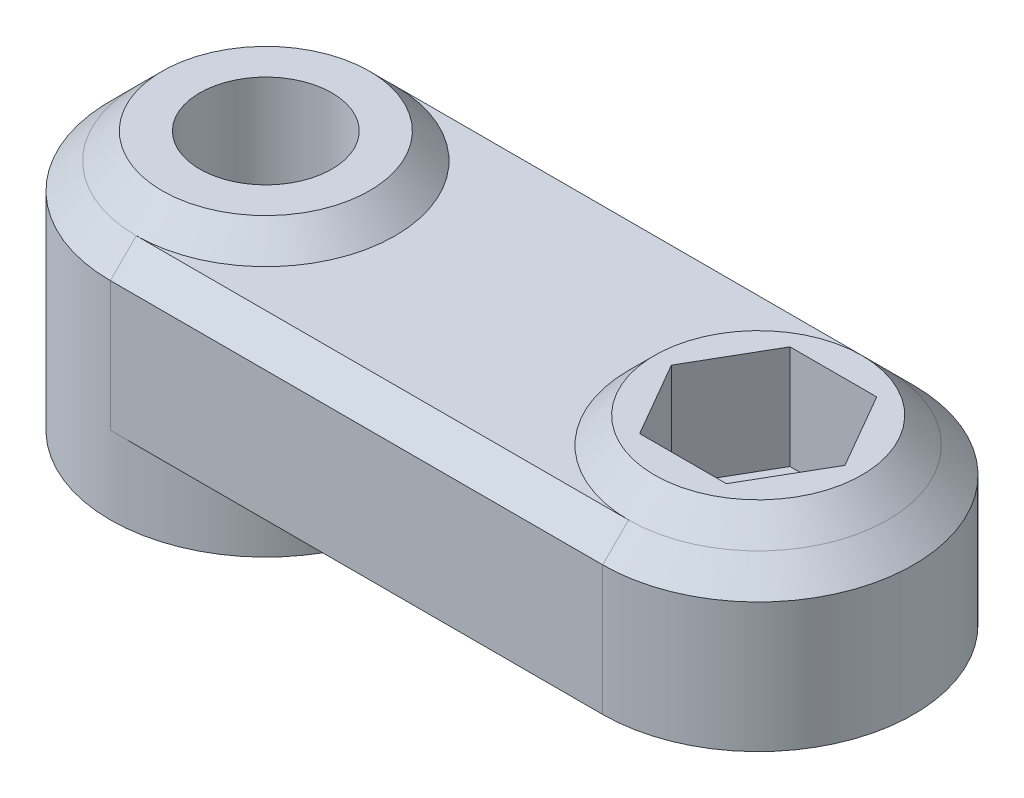
SolidWorks part; units mm, degrees
ref_plane "前视基准面" through (0, 0, 0) normal (0, 0, 1) x (1, 0, 0)
ref_plane "上视基准面" through (0, 0, 0) normal (0, 1, 0) x (1, 0, 0)
ref_plane "右视基准面" through (0, 0, 0) normal (1, 0, 0) x (0, 0, -1)
sketch "草图1" plane through (0, 0, 0) normal (0, 1, 0) x (1, 0, 0)
  line L0 (0, 0) -> (19, 0) construction
  line L1 (0, 6) -> (19, 6)
  line L2 (0, -6) -> (19, -6)
  arc A0 (0, 6) -> (0, -6) centre (0, 0) ccw
  arc A1 (19, -6) -> (19, 6) centre (19, 0) ccw
  point P3 (9.5, 0)
  dimension "D1" = 19
  dimension "D2" = 12
extrude "凸台-拉伸1" add sketch "草图1" along normal blind 10
sketch "草图2" plane through (0, 0, 0) normal (0, 0, 1) x (1, 0, 0)
  line L0 (0, -1.4276) -> (0, 12.6969) construction
  line L1 (0, 10) -> (-2.55, 10)
  line L2 (0, 10) -> (-6, 10) construction
  line L3 (-2.55, 10) -> (-2.55, 5)
  line L4 (-2.55, 5) -> (-1.6, 5)
  line L5 (-1.6, 5) -> (-1.6, 2)
  line L6 (-1.6, 2) -> (-2.55, 2)
  line L7 (-2.55, 2) -> (-2.55, 0)
  line L8 (-6, 0) -> (0, 0) construction
  line L9 (-2.55, 0) -> (0, 0)
  line L10 (0, 10) -> (0, 0)
  dimension "D1" = 5.1
  dimension "D2" = 5
  dimension "D3" = 3.2
  dimension "D4" = 3
revolve "切除-旋转1" cut sketch "草图2" angle 360 about L0
sketch "草图3" plane through (0, 0, 0) normal (0, 0, 1) x (1, 0, 0)
  line L0 (19, 0) -> (19, 10) construction
  line L1 (19, 0) -> (16.925, 0)
  line L2 (0, 0) -> (19, 0) construction
  line L3 (16.925, 0) -> (16.925, 6)
  line L4 (16.925, 6) -> (16.5, 6)
  line L5 (16.5, 6) -> (16.5, 10)
  line L6 (0, 10) -> (19, 10) construction
  line L7 (16.5, 10) -> (19, 10)
  line L8 (19, 0) -> (19, 10)
  dimension "D1" = 4.15
  dimension "D2" = 6
  dimension "D3" = 5
revolve "切除-旋转2" cut sketch "草图3" angle 360 about L0
chamfer "倒角1" distance 2 angle 45 4 edges at (9.5, 10, -6) (-6, 10, 0) (25, 10, 0) (9.5, 10, 6)
sketch "草图4" plane through (0, 0, 0) normal (0, -1, 0) x (1, 0, 0)
  line L0 (0, 6) -> (19, 6) construction
  line L1 (2.1073, 3.65) -> (-2.1073, 3.65)
  line L2 (-2.1073, 3.65) -> (-4.2147, 0)
  line L3 (-4.2147, 0) -> (-2.1073, -3.65)
  line L4 (-2.1073, -3.65) -> (2.1073, -3.65)
  line L5 (2.1073, -3.65) -> (4.2147, 0)
  line L6 (4.2147, 0) -> (2.1073, 3.65)
  circle A0 centre (0, 0) radius 3.65 construction
  dimension "D1" = 7.3
extrude "切除-拉伸1" cut sketch "草图4" against normal blind 5
sketch "草图5" plane through (0, 0, 0) normal (0, -1, 0) x (1, 0, 0)
  circle A0 centre (0, 0) radius 6
  circle A1 centre (0, 0) radius 32.436
  arc A2 (0, 6) -> (0, -6) centre (0, 0) ccw construction
extrude "切除-拉伸2" cut sketch "草图5" against normal blind 3
sketch "草图6" plane through (0, 10, 0) normal (0, 1, 0) x (1, 0, 0)
  line L0 (19, 4) -> (0, 4) construction
  line L1 (20.6743, 2.9) -> (17.3257, 2.9)
  line L2 (17.3257, 2.9) -> (15.6514, 0)
  line L3 (15.6514, 0) -> (17.3257, -2.9)
  line L4 (17.3257, -2.9) -> (20.6743, -2.9)
  line L5 (20.6743, -2.9) -> (22.3486, 0)
  line L6 (22.3486, 0) -> (20.6743, 2.9)
  circle A0 centre (19, 0) radius 2.9 construction
  dimension "D1" = 5.8
extrude "切除-拉伸3" cut sketch "草图6" against normal blind 4
sketch "草图7" plane through (0, 10, 0) normal (0, 1, 0) x (1, 0, 0)
  line L1 (33.7128, -22.6227) -> (-20.3488, -22.6227)
  line L2 (33.7128, -22.6227) -> (33.7128, 24.9049)
  line L3 (33.7128, 24.9049) -> (-20.3488, 24.9049)
  line L4 (-20.3488, -22.6227) -> (-20.3488, 24.9049)
  circle A0 centre (0, 0) radius 4
  circle A1 centre (19, 0) radius 4
extrude "切除-拉伸4" cut sketch "草图7" against normal blind 1
chamfer "倒角2" distance 1 angle 45 2 edges at (19, 9, 4) (0, 9, 4)
